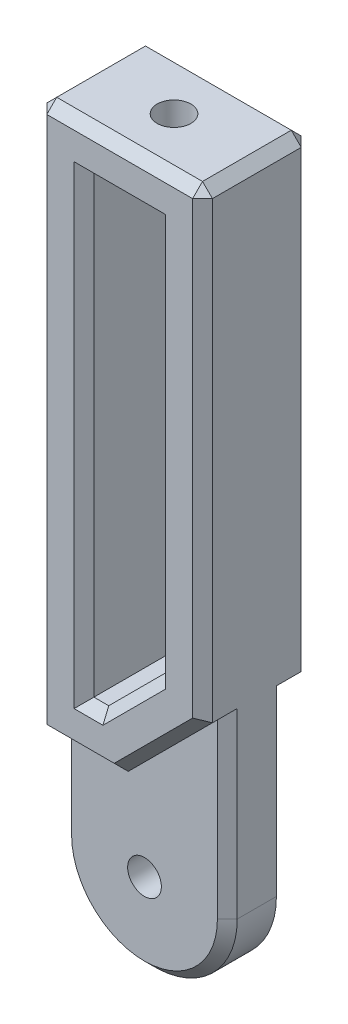
SolidWorks part; units mm, degrees
ref_plane "Front Plane" through (0, 0, 0) normal (0, 0, 1) x (1, 0, 0)
ref_plane "Top Plane" through (0, 0, 0) normal (0, 1, 0) x (1, 0, 0)
ref_plane "Right Plane" through (0, 0, 0) normal (1, 0, 0) x (0, 0, -1)
sketch "Sketch1" plane through (0, 0, 0) normal (0, 0, 1) x (1, 0, 0)
  line L2 (-8.35, 0) -> (-8.35, 65.15)
  line L3 (-8.35, 65.15) -> (8.35, 65.15)
  line L4 (8.35, 0) -> (8.35, 65.15)
  arc A1 (-8.35, 0) -> (8.35, 0) centre (0, 0) ccw
  dimension "D2" = 8.35
  dimension "D1" = 65.15
extrude "Boss-Extrude1" add sketch "Sketch1" along normal mid plane 5.95
sketch "Sketch4" plane through (0, 0, 2.975) normal (0, 0, 1) x (1, 0, 0)
  line L0 (-8.35, 65.15) -> (-8.35, 9.9)
  line L1 (-8.35, 65.15) -> (-8.35, 0) construction
  line L2 (-8.35, 9.9) -> (-0.1353, 9.9)
  line L3 (-0.1353, 9.9) -> (8.35, 18.3853)
  line L4 (8.35, 0) -> (8.35, 65.15) construction
  line L5 (8.35, 18.3853) -> (8.35, 65.15)
  line L6 (8.35, 65.15) -> (-8.35, 65.15)
  line L7 (-0.1353, 9.9) -> (8.35, 9.9) construction
  dimension "D1" = 45
  dimension "D2" = 55.25
  dimension "D3" = 12
extrude "Boss-Extrude2" add sketch "Sketch4" along normal blind 2.5
extrude "Boss-Extrude3" add sketch "Sketch4<2>" against normal blind 2.5 from surface starting at face at (0, 30.4875, -2.975)
sketch "Sketch4<2>" plane through (0, 0, 2.975) normal (0, 0, 1) x (1, 0, 0) same geometry as "Sketch4"
sketch "Sketch5" plane through (0, 0, 5.475) normal (0, 0, 1) x (1, 0, 0)
  line L5 (-3.6, 14.65) -> (-2.1028, 14.65)
  line L8 (-3.6, 14.65) -> (-2.1028, 14.65)
  line L10 (3.6, 60.4) -> (-3.6, 60.4)
  line L11 (-3.6, 60.4) -> (-3.6, 14.65)
  line L13 (-2.1028, 14.65) -> (3.6, 20.3528)
  line L14 (3.6, 20.3528) -> (3.6, 60.4)
  line L15 (3.6, 60.4) -> (-3.6, 60.4)
  line L16 (-3.6, 60.4) -> (-3.6, 14.65)
  line L18 (-2.1028, 14.65) -> (3.6, 20.3528)
  line L19 (3.6, 20.3528) -> (3.6, 60.4)
  dimension "D1" = 4.75
extrude "Cut-Extrude3" cut sketch "Sketch5" against normal through all
sketch "Sketch6" plane through (0, 60.4, 0) normal (0, -1, 0) x (1, 0, 0)
  line L0 (8.35, -5.475) -> (-8.35, -5.475) construction
  line L1 (-8.35, 5.475) -> (-8.35, -5.475) construction
  circle A0 centre (0, 0) radius 1.7
  point P4 (0, -5.475)
  point P7 (-8.35, 0)
  dimension "D1" = 3.4
extrude "Cut-Extrude4" cut sketch "Sketch6" against normal through all
sketch "Sketch7" plane through (0, 0, 2.975) normal (0, 0, 1) x (1, 0, 0)
  circle A0 centre (0, 0) radius 1.7
  arc A1 (-8.35, 0) -> (8.35, 0) centre (0, 0) ccw construction
  dimension "D1" = 3.4
extrude "Cut-Extrude5" cut sketch "Sketch7" against normal through all
chamfer "Chamfer1" distance 1 angle 45 28 edges at (8.35, 41.7676, -5.475) (0, 65.15, -5.475) (-8.35, 37.525, -5.475) (-4.2426, 9.9, -5.475) (4.1074, 14.1426, -5.475) (-2.8514, 14.65, -5.475) (-3.6, 37.525, -5.475) (0, 60.4, -5.475) (3.6, 40.3764, -5.475) (0.7486, 17.5014, -5.475) (0, 65.15, 5.475) (8.35, 41.7676, 5.475) (4.1074, 14.1426, 5.475) (-4.2426, 9.9, 5.475) (-8.35, 37.525, 5.475) (-2.8514, 14.65, 5.475) (0.7486, 17.5014, 5.475) (3.6, 40.3764, 5.475) (0, 60.4, 5.475) (-3.6, 37.525, 5.475) (-8.35, 4.95, -2.975) (0, -8.35, -2.975) (8.35, 9.1926, -2.975) (-8.35, 4.95, 2.975) (0, -8.35, 2.975) (8.35, 9.1926, 2.975) (-8.35, 65.15, 0) (8.35, 65.15, 0)
